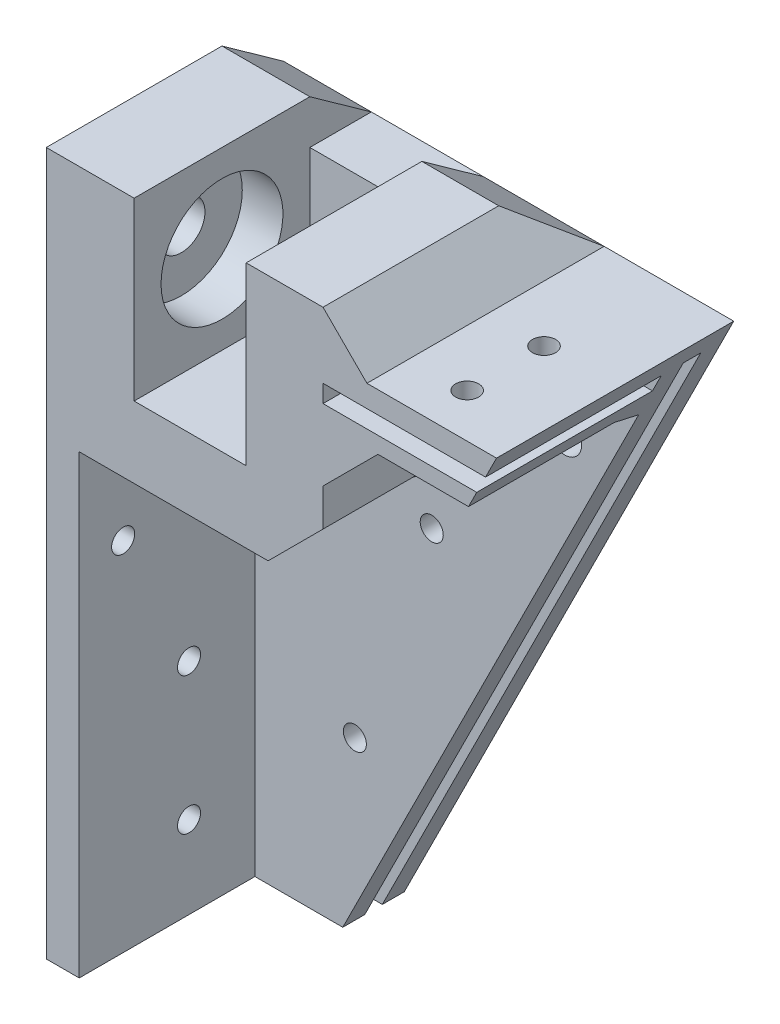
SolidWorks part; units mm, degrees
material "ABS"
ref_plane "Płaszczyzna przednia" through (0, 0, 0) normal (0, 0, 1) x (1, 0, 0)
ref_plane "Płaszczyzna górna" through (0, 0, 0) normal (0, 1, 0) x (1, 0, 0)
ref_plane "Płaszczyzna prawa" through (0, 0, 0) normal (1, 0, 0) x (0, 0, -1)
sketch "Szkic1" plane through (0, 0, 0) normal (0, 0, 1) x (1, 0, 0)
  line L0 (0, 0) -> (80, 0)
  line L1 (0, 0) -> (0, -120)
  line L2 (80, 0) -> (20, -120)
  line L3 (20, -120) -> (0, -120)
  dimension "D1" = 80
  dimension "D2" = 120
  dimension "D3" = 20
extrude "Dodanie-wyciągnięcie1" add sketch "Szkic1" along normal blind 4
sketch "Szkic2" plane through (0, 0, 4) normal (0, 0, 1) x (1, 0, 0)
  line L0 (80, 0) -> (0, 0) construction
  line L1 (0, 0) -> (0, -120) construction
  line L2 (80, 0) -> (0, 0)
  line L3 (0, 0) -> (0, -120)
  line L4 (78, -4) -> (4, -4)
  line L5 (4, -4) -> (4, -120)
  line L6 (4, -120) -> (0, -120)
  line L7 (80, 0) -> (78, -4)
  line L9 (80, -4) -> (4, -4) construction
  dimension "D1" = 4
extrude "Dodanie-wyciągnięcie2" add sketch "Szkic2" along normal blind 3.2
sketch "Szkic3" plane through (0, 0, 7.2) normal (0, 0, 1) x (1, 0, 0)
  line L0 (78, -4) -> (80, 0) construction
  line L1 (0, -120) -> (4, -120) construction
  line L2 (4, -120) -> (20, -120) construction
  line L3 (20, -120) -> (78, -4) construction
  line L4 (80, 0) -> (0, 0) construction
  line L5 (0, 0) -> (0, -120) construction
  line L6 (78, -4) -> (80, 0)
  line L7 (0, -120) -> (4, -120)
  line L8 (4, -120) -> (20, -120)
  line L9 (20, -120) -> (78, -4)
  line L10 (80, 0) -> (0, 0)
  line L11 (0, 0) -> (0, -120)
extrude "Dodanie-wyciągnięcie3" add sketch "Szkic3" along normal blind 4
sketch "Szkic4" plane through (0, 0, 11.2) normal (0, 0, 1) x (1, 0, 0)
  line L0 (0, 8) -> (0, -37)
  line L1 (0, 0) -> (0, -120) construction
  line L3 (14, -24) -> (14, 8)
  line L6 (34.4, -24) -> (34.4, 8)
  line L7 (80, 0) -> (0, 0) construction
  line L8 (48.4, 8) -> (48.4, -37)
  line L9 (0, 8) -> (14, 8)
  line L10 (34.4, 8) -> (48.4, 8)
  line L11 (0, -37) -> (48.4, -37)
  line L12 (14, -24) -> (34.4, -24)
  dimension "D1" = 45
  dimension "D2" = 14
  dimension "D3" = 20.4
  dimension "D4" = 14
  dimension "D5" = 8
  dimension "D6" = 32
extrude "Dodanie-wyciągnięcie4" add sketch "Szkic4" along normal blind 32
ref_plane "Płaszczyzna1" through (24.2, 0, 0) normal (1, 0, 0) x (0, 0, -1)
sketch "Szkic5" plane through (24.2, 0, 0) normal (1, 0, 0) x (0, 0, -1)
  line L0 (-11.2, -120) -> (-11.2, 0) construction
  line L1 (-43.2, 8) -> (-11.2, 8) construction
  circle A0 centre (-27.2, -8) radius 11.1
  dimension "D1" = 22.2
  dimension "D3" = 16
  dimension "D2" = 16
extrude "Wytnij-wyciągnięcie1" cut sketch "Szkic5" against normal blind 17.6 and the other way blind 17.6
chamfer "Sfazowanie1" distance 11.2 distance2 8 2 edges at (7, 0, 11.2) (41.4, 0, 11.2) first distance on face at (36.6857, 0, 8)
sketch "Szkic6" plane through (24.2, 0, 0) normal (1, 0, 0) x (0, 0, -1)
  circle A0 centre (-27.2, -8) radius 11.1 construction
  circle A1 centre (-27.2, -8) radius 11.1 construction
  circle A2 centre (-27.2, -8) radius 4.3
  dimension "D1" = 8.6
extrude "Wytnij-wyciągnięcie2" cut sketch "Szkic6" against normal through all and the other way blind 20.2
sketch "Szkic7" plane through (0, 0, 11.2) normal (0, 0, 1) x (1, 0, 0)
  line L0 (0, -37) -> (0, -120)
  line L1 (0, -120) -> (20, -120) construction
  line L2 (0, -37) -> (0, -120) construction
  line L3 (0, -120) -> (4, -120)
  line L4 (4, -120) -> (4, -37)
  line L5 (0, -37) -> (48.4, -37) construction
  line L6 (4, -37) -> (0, -37)
  line L11 (0, -37) -> (48.4, -37) construction
  line L12 (7.2, -37) -> (10.2, -37)
  line L13 (7.2, -37) -> (7.2, -120)
  line L14 (7.2, -120) -> (10.2, -120)
  line L15 (10.2, -37) -> (10.2, -120)
  line L16 (48.4, 0) -> (80, 0)
  line L17 (80, 0) -> (78, -4)
  line L18 (20, -120) -> (80, 0) construction
  line L19 (78, -4) -> (48.4, -4)
  line L20 (48.4, -37) -> (48.4, 0) construction
  line L21 (48.4, -4) -> (48.4, 0)
  line L22 (48.4, -7.2) -> (76.4, -7.2)
  line L23 (76.4, -7.2) -> (74.9, -10.2)
  line L24 (74.9, -10.2) -> (48.4, -10.2)
  line L25 (48.4, -10.2) -> (48.4, -7.2)
  dimension "D1" = 4
  dimension "D2" = 3
  dimension "D3" = 3.2
  dimension "D4" = 4
  dimension "D5" = 3
  dimension "D6" = 3.2
extrude "Dodanie-wyciągnięcie5" add sketch "Szkic7" along normal blind 32
chamfer "Sfazowanie2" distance 10 angle 45 3 edges at (48.4, -37, 27.2) (48.4, -10.2, 27.2) (10.2, -37, 27.2)
chamfer "Sfazowanie3" distance 2 angle 70 7 edges at (66.65, -10.2, 11.2) (53.4, -15.2, 11.2) (48.4, -23.6, 11.2) (43.4, -32, 11.2) (29.3, -37, 11.2) (15.2, -42, 11.2) (10.2, -83.5, 11.2) first distance on face at (36.5667, -47.6222, 11.2)
sketch "Szkic8" plane through (0, -10.2, 0) normal (0, -1, 0) x (1, 0, 0)
  line L0 (58.4, 43.2) -> (74.9, 43.2) construction
  line L1 (20, 11.2) -> (73.9, 11.2) construction
  line L2 (58.4, 43.2) -> (58.4, 16.695) construction
  circle A0 centre (66.65, 35.2) radius 2.1
  circle A1 centre (66.65, 21.2) radius 2.1
  dimension "D3" = 4.2
  dimension "D1" = 8
  dimension "D2" = 10
  dimension "D4" = 8.25
extrude "Otwory tyl" cut sketch "Szkic8" against normal through all
sketch "Szkic9" plane through (0, 0, 11.2) normal (0, 0, 1) x (1, 0, 0)
  line L0 (50.4, -21.0284) -> (50.4, -27.8284) construction
  line L1 (73.9, -12.2) -> (59.2284, -12.2) construction
  line L2 (12.2, -47.8284) -> (12.2, -120) construction
  line L3 (39.2284, -39) -> (21.0284, -39) construction
  circle A0 centre (60.4, -22.2) radius 3.1
  circle A1 centre (22.2, -49) radius 2.1
  circle A2 centre (22.2, -89) radius 2.1
  circle A3 centre (36.2, -49) radius 2.1
  dimension "D1" = 4.2
  dimension "D2" = 6.2
  dimension "D3" = 10
  dimension "D4" = 10
  dimension "D5" = 10
  dimension "D6" = 40
  dimension "D7" = 14
  dimension "D8" = 10
extrude "Otwory spod" cut sketch "Szkic9" against normal through all
sketch "Szkic10" plane through (10.2, 0, 0) normal (1, 0, 0) x (0, 0, -1)
  line L0 (-43.2, -120) -> (-43.2, -47) construction
  line L1 (-11.2, -47.8284) -> (-11.2, -120) construction
  line L2 (-16.695, -47) -> (-43.2, -47) construction
  circle A0 centre (-23.2, -80) radius 2.1
  circle A1 centre (-35.2, -55) radius 2.1
  circle A2 centre (-23.2, -105) radius 2.1
  dimension "D7" = 4.2
  dimension "D1" = 8
  dimension "D2" = 12
  dimension "D3" = 8
  dimension "D4" = 25
  dimension "D5" = 25
  dimension "D6" = 12
extrude "Otwory bok" cut sketch "Szkic10" against normal through all
chamfer "Sfazowanie4" distance 8 angle 45 1 edges at (48.4, 0, 21.6)
sketch "Szkic12" plane through (0, 0, 43.2) normal (0, 0, 1) x (1, 0, 0)
  line L1 (7.2, -37) -> (21.0284, -37)
  line L2 (7.2, -37) -> (7.2, -124.1298)
  line L3 (7.2, -124.1298) -> (21.0284, -124.1298)
  line L4 (21.0284, -37) -> (21.0284, -124.1298)
extrude "Wytnij-wyciągnięcie5" cut sketch "Szkic12" against normal up to surface (32 mm away) up to face at (63.5, -22.2, 11.2)
sketch "Szkic13" plane through (0, 0, 0) normal (-1, 0, 0) x (0, 0, 1)
  line L5 (0, -120) -> (43.2, -120)
  line L6 (43.2, -120) -> (43.2, 8)
  line L7 (43.2, 8) -> (11.2, 8)
  line L8 (11.2, 8) -> (0, 0)
  line L9 (0, 0) -> (0, -120)
  line L10 (0, -120) -> (43.2, -120)
  line L11 (43.2, -120) -> (43.2, 8)
  line L12 (43.2, 8) -> (11.2, 8)
  line L13 (11.2, 8) -> (0, 0)
  line L14 (0, 0) -> (0, -120)
  circle A0 centre (23.2, -105) radius 2.1 construction
  circle A1 centre (23.2, -80) radius 2.1 construction
  circle A2 centre (35.2, -55) radius 2.1 construction
  circle A3 centre (27.2, -8) radius 4.3 construction
  circle A4 centre (23.2, -105) radius 2.1
  circle A5 centre (23.2, -80) radius 2.1
  circle A6 centre (35.2, -55) radius 2.1
  circle A7 centre (27.2, -8) radius 4.3
  dimension "D1" = 0
extrude "Dodanie-wyciągnięcie6" add sketch "Szkic13" along normal blind 2
sketch "Szkic14" plane through (-2, 0, 0) normal (-1, 0, 0) x (0, 0, 1)
  line L0 (43.2, -37) -> (11.2, -37) construction
  line L1 (43.2, -37) -> (11.2, -37)
  line L2 (43.2, -24) -> (11.2, -24) construction
  line L3 (43.2, -24) -> (11.2, -24)
  line L4 (43.2, -120) -> (43.2, 8) construction
  circle A0 centre (35.2, -30.5) radius 2
  circle A1 centre (27.2, -30.5) radius 2
  point P10 (0, 0)
  dimension "D1" = 4
  dimension "D3" = 8
  dimension "D4" = 4
  dimension "D2" = 8
  dimension "D5" = 6.5
extrude "Wytnij-wyciągnięcie6" cut sketch "Szkic14" against normal blind 5 contours A1 | A0 region at (-2, -30.5, 35.2) region at (-2, -30.5, 27.2)
